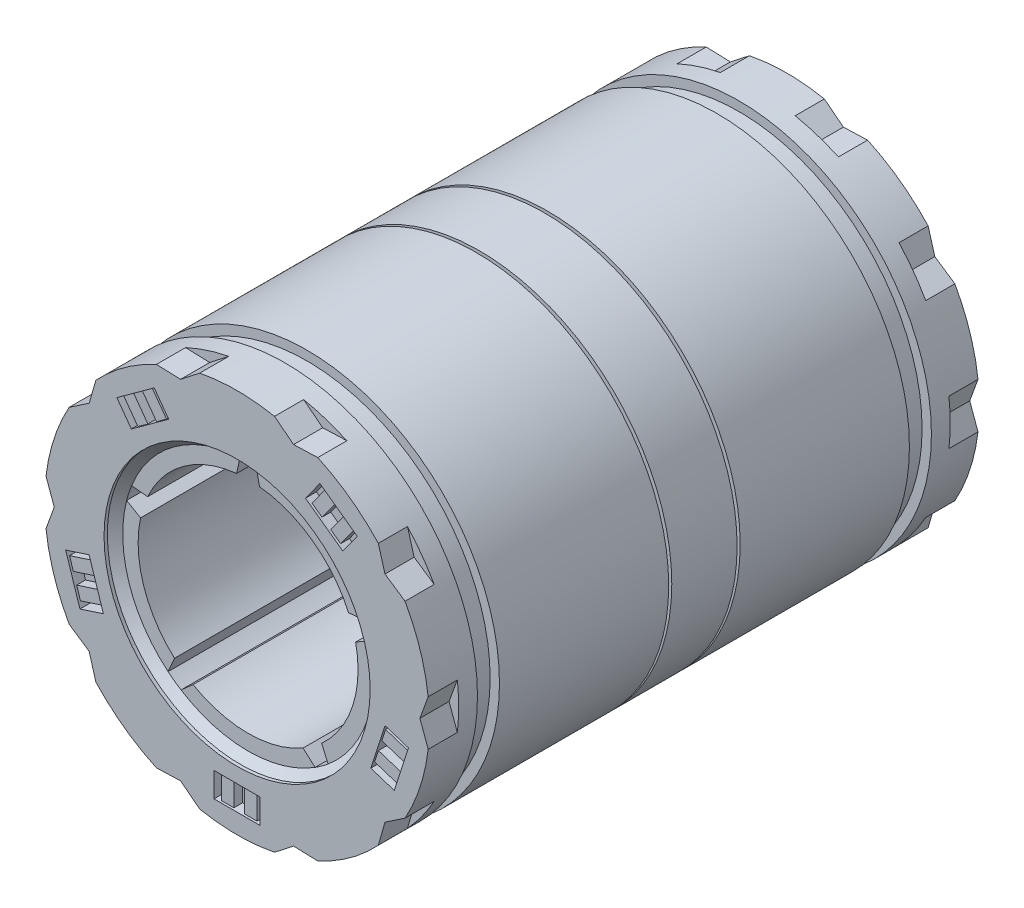
SolidWorks part; units mm, degrees
material "POM Acetal Copolymer"
ref_plane "Front Plane" through (0, 0, 0) normal (0, 0, 1) x (1, 0, 0)
ref_plane "Top Plane" through (0, 0, 0) normal (0, 1, 0) x (1, 0, 0)
ref_plane "Right Plane" through (0, 0, 0) normal (1, 0, 0) x (0, 0, -1)
sketch "Sketch1" plane through (0, 0, 0) normal (0, 0, 1) x (1, 0, 0)
  line L0 (0, 0) -> (-5.5562, -9.6237) construction
  line L2 (5.5562, -9.6237) -> (0, 0) construction
  circle A0 centre (0, 0) radius 11.1125
  circle A1 centre (0, 0) radius 6.35
  point P4 (-3.175, -5.4993)
  point P5 (3.175, -5.4993)
  dimension "OD" = 22.225
  dimension "ID" = 12.7
  dimension "a" = 60
  dimension "Width" = 6.35
sketch "Sketch2" plane through (0, 0, 0) normal (1, 0, 0) x (0, 0, -1)
  line L0 (-15.875, 0) -> (15.875, 0) construction
  line L1 (0, -11.1125) -> (0, 11.1125) construction
  line L3 (-13.1064, 11.1125) -> (-11.8364, 11.1125)
  line L4 (-13.1064, 11.1125) -> (-13.1064, 10.574)
  line L5 (-13.1064, 10.574) -> (-11.8364, 10.574)
  line L6 (-11.8364, 11.1125) -> (-11.8364, 10.574)
  point P3 (-13.1064, 0)
  point P5 (13.1064, 0)
  point P10 (-11.8364, 0)
  dimension "Overall Length" = 31.75
  dimension "Retaining Ring Groove End to End Length" = 26.2128
  dimension "Groove Thickness" = 1.27
  dimension "Groove Depth" = 0.5385
sketch "Sketch3" plane through (0, 0, 0) normal (1, 0, 0) x (0, 0, -1)
  line L0 (-15.875, 6.35) -> (-15.875, 11.1125)
  line L1 (-15.875, 11.1125) -> (-13.1064, 11.1125)
  line L2 (-13.1064, 11.1125) -> (-13.1064, 10.574)
  line L3 (-13.1064, 10.574) -> (-11.8364, 10.574)
  line L4 (-11.8364, 10.574) -> (-11.8364, 11.1125)
  line L5 (-11.8364, 11.1125) -> (-2.0637, 11.1125)
  line L6 (11.8364, 11.1125) -> (11.8364, 10.574)
  line L7 (11.8364, 10.574) -> (13.1064, 10.574)
  line L8 (13.1064, 10.574) -> (13.1064, 11.1125)
  line L9 (13.1064, 11.1125) -> (15.875, 11.1125)
  line L10 (15.875, 11.1125) -> (15.875, 6.35)
  line L11 (15.875, 6.35) -> (-15.875, 6.35)
  line L14 (-2.0637, 11.1125) -> (-2.0637, 10.668)
  line L15 (-2.0637, 10.668) -> (-1.8859, 10.668)
  line L16 (-1.8859, 10.668) -> (-1.8859, 11.1125)
  line L17 (1.886, 11.1125) -> (1.886, 10.668)
  line L18 (1.886, 10.668) -> (2.0638, 10.668)
  line L19 (2.0638, 10.668) -> (2.0638, 11.1125)
  line L20 (-1.8859, 11.1125) -> (1.886, 11.1125)
  line L21 (2.0638, 11.1125) -> (11.8364, 11.1125)
  point P17 (0, 6.35)
  point P30 (0, 11.1125)
  dimension "D1" = 4.1275
  dimension "D2" = 0.4445
  dimension "D3" = 0.1778
revolve "Revolve1" add sketch "Sketch3" angle 360 about L0
sketch "Sketch4" plane through (0, 0, 0) normal (0, 0, 1) x (1, 0, 0)
  line L0 (-3.175, -5.4993) -> (-3.8723, -6.1162)
  line L2 (-6.2112, 1.3202) -> (-7.0135, 1.7928)
  line L3 (3.175, -5.4993) -> (3.8723, -6.1162)
  line L5 (-4.249, -4.719) -> (-4.6202, -5.5728)
  line L6 (-0.6638, 6.3152) -> (-0.4622, 7.2242)
  line L7 (-5.801, 2.5828) -> (-6.7278, 2.672)
  line L8 (5.801, 2.5828) -> (6.7278, 2.672)
  line L9 (0.6638, 6.3152) -> (0.4622, 7.2242)
  line L10 (4.249, -4.719) -> (4.6202, -5.5728)
  line L11 (6.2112, 1.3202) -> (7.0135, 1.7928)
  arc A0 (0.4622, 7.2242) -> (-0.4622, 7.2242) centre (0, 0) ccw
  circle A1 centre (0, 0) radius 6.35 construction
  arc A2 (-5.801, 2.5828) -> (-6.2112, 1.3202) centre (0, 0) ccw
  arc A11 (-6.7278, 2.672) -> (-7.0135, 1.7928) centre (0, 0) ccw
  arc A12 (-7.0204, 1.7657) -> (-4.6418, -5.5549) centre (0, 0) ccw construction
  arc A13 (4.6418, -5.5549) -> (7.0204, 1.7657) centre (0, 0) ccw construction
  arc A14 (6.7174, 2.698) -> (0.4902, 7.2224) centre (0, 0) ccw construction
  arc A15 (4.249, -4.719) -> (6.2112, 1.3202) centre (0, 0) ccw construction
  arc A16 (5.801, 2.5828) -> (0.6638, 6.3152) centre (0, 0) ccw construction
  arc A17 (-0.6638, 6.3152) -> (-5.801, 2.5828) centre (0, 0) ccw construction
  arc A18 (-6.2112, 1.3202) -> (-4.249, -4.719) centre (0, 0) ccw construction
  arc A19 (-0.4902, 7.2224) -> (-6.7174, 2.698) centre (0, 0) ccw construction
  arc A20 (7.0135, 1.7928) -> (6.7278, 2.672) centre (0, 0) ccw
  arc A21 (3.8723, -6.1162) -> (4.6202, -5.5728) centre (0, 0) ccw
  arc A22 (-4.6202, -5.5728) -> (-3.8723, -6.1162) centre (0, 0) ccw
  arc A23 (0.6638, 6.3152) -> (-0.6638, 6.3152) centre (0, 0) ccw
  arc A24 (6.2112, 1.3202) -> (5.801, 2.5828) centre (0, 0) ccw
  arc A25 (3.175, -5.4993) -> (4.249, -4.719) centre (0, 0) ccw
  arc A26 (-4.249, -4.719) -> (-3.175, -5.4993) centre (0, 0) ccw
  point P31 (0, 0)
  dimension "D1" = 0.889
  dimension "D3" = 25
  dimension "D2" = 5
extrude "Cut-Extrude1" cut sketch "Sketch4" against normal through all both and the other way through all
sketch "Sketch5" plane through (0, 0, 0) normal (0, 0, 1) x (1, 0, 0)
  circle A0 centre (0, 0) radius 7.6835
  circle A1 centre (0, 0) radius 6.35 construction
  dimension "D1" = 1.3335
extrude "Cut-Extrude2" cut sketch "Sketch5" against normal blind 0.635 from surface starting at face at (0, 0, 15.875)
extrude "Cut-Extrude3" cut sketch "Sketch5<2>" along normal blind 0.635 from surface starting at face at (11.1125, 0, -15.875)
sketch "Sketch5<2>" plane through (0, 0, 0) normal (0, 0, 1) x (1, 0, 0) same geometry as "Sketch5"
chamfer "Chamfer1" distance 0.4445 angle 45 2 edges at (-7.6835, 0, 15.24) (7.6835, 0, -15.24)
sketch "Sketch8" plane through (0, 0, 0) normal (0, 0, 1) x (1, 0, 0)
  line L0 (-4.6584, 10.0889) -> (-3.2623, 10.0402)
  line L1 (-3.2623, 10.0402) -> (-2.1614, 10.9003)
  line L2 (0, 0) -> (0, 10.5569) construction
  line L3 (0, 0) -> (-3.2623, 10.0402) construction
  line L4 (2.1614, 10.9003) -> (3.2623, 10.0402)
  line L5 (3.2623, 10.0402) -> (4.6584, 10.0889)
  line L6 (8.1556, 7.5481) -> (8.5407, 6.2052)
  line L7 (8.5407, 6.2052) -> (9.6989, 5.424)
  line L8 (11.0347, 1.3128) -> (10.5569, 0)
  line L9 (10.5569, 0) -> (11.0347, -1.3128)
  line L10 (9.6989, -5.424) -> (8.5407, -6.2052)
  line L11 (8.5407, -6.2052) -> (8.1556, -7.5481)
  line L12 (4.6584, -10.0889) -> (3.2623, -10.0402)
  line L13 (3.2623, -10.0402) -> (2.1614, -10.9003)
  line L14 (-2.1614, -10.9003) -> (-3.2623, -10.0402)
  line L15 (-3.2623, -10.0402) -> (-4.6584, -10.0889)
  line L16 (-8.1556, -7.5481) -> (-8.5407, -6.2052)
  line L17 (-8.5407, -6.2052) -> (-9.6989, -5.424)
  line L18 (-11.0347, -1.3128) -> (-10.5569, 0)
  line L19 (-10.5569, 0) -> (-11.0347, 1.3128)
  line L20 (-9.6989, 5.424) -> (-8.5407, 6.2052)
  line L21 (-8.5407, 6.2052) -> (-8.1556, 7.5481)
  circle A0 centre (0, 0) radius 11.1125 construction
  circle A1 centre (0, 0) radius 10.5569 construction
  arc A2 (-2.1614, 10.9003) -> (-4.6584, 10.0889) centre (0, 0) ccw
  arc A3 (4.6584, 10.0889) -> (2.1614, 10.9003) centre (0, 0) ccw
  arc A4 (9.6989, 5.424) -> (8.1556, 7.5481) centre (0, 0) ccw
  arc A5 (11.0347, -1.3128) -> (11.0347, 1.3128) centre (0, 0) ccw
  arc A6 (8.1556, -7.5481) -> (9.6989, -5.424) centre (0, 0) ccw
  arc A7 (2.1614, -10.9003) -> (4.6584, -10.0889) centre (0, 0) ccw
  arc A8 (-4.6584, -10.0889) -> (-2.1614, -10.9003) centre (0, 0) ccw
  arc A9 (-9.6989, -5.424) -> (-8.1556, -7.5481) centre (0, 0) ccw
  arc A10 (-11.0347, 1.3128) -> (-11.0347, -1.3128) centre (0, 0) ccw
  arc A11 (-8.1556, 7.5481) -> (-9.6989, 5.424) centre (0, 0) ccw
  point P38 (0, 0)
  dimension "D1" = 140
  dimension "D2" = 0.5556
  dimension "D3" = 10
extrude "Cut-Extrude5" cut sketch "Sketch8" against normal blind 1.6827 from surface starting at face at (-7.6835, 0, 15.875)
extrude "Cut-Extrude6" cut sketch "Sketch8<2>" along normal blind 1.6827 from surface starting at face at (7.6835, 0, -15.875)
sketch "Sketch8<2>" plane through (0, 0, 0) normal (0, 0, 1) x (1, 0, 0) same geometry as "Sketch8"
sketch "Sketch9" plane through (0, 0, 0) normal (0, 0, 1) x (1, 0, 0)
  line L0 (0, -11.1125) -> (0, -9.9746) construction
  line L1 (-1.3335, -8.5522) -> (-1.0223, -8.5522)
  line L2 (-1.3335, -8.5522) -> (-1.3335, -9.9746)
  line L3 (-1.3335, -9.9746) -> (-1.0223, -9.9746)
  line L4 (1.3335, -8.5522) -> (1.3335, -9.9746)
  line L5 (-1.0223, -8.5522) -> (-1.0223, -9.9746)
  line L6 (-1.3335, -9.2634) -> (-1.0224, -9.2634) construction
  line L7 (-0.3111, -8.5522) -> (-0.3111, -9.9746)
  line L8 (-1.0224, -9.2634) -> (-0.3111, -9.2634) construction
  line L9 (0.3111, -8.5522) -> (0.3111, -9.9746)
  line L10 (-0.3111, -9.2634) -> (0, -9.2634) construction
  line L11 (1.0224, -8.5522) -> (1.0224, -9.9746)
  line L12 (0.3111, -9.2634) -> (1.0224, -9.2634) construction
  line L13 (1.0224, -9.2634) -> (1.3335, -9.2634) construction
  line L14 (0, -9.2634) -> (0.3111, -9.2634) construction
  line L15 (-0.3111, -8.5522) -> (0.3111, -8.5522)
  line L16 (1.0224, -8.5522) -> (1.3335, -8.5522)
  line L17 (1.0224, -9.9746) -> (1.3335, -9.9746)
  line L18 (-0.3111, -9.9746) -> (0.3111, -9.9746)
  circle A1 centre (0, 0) radius 11.1125 construction
  dimension "D1" = 2.667
  dimension "D2" = 1.4224
  dimension "D3" = 1.1379
  dimension "D4" = 0.7112
extrude "Cut-Extrude7" cut sketch "Sketch9" against normal blind 0.635 from surface starting at face at (-7.6835, 0, 15.875)
sketch "Sketch10" plane through (0, 0, 0) normal (0, 0, 1) x (1, 0, 0)
  line L1 (-1.3335, -8.5522) -> (1.3335, -8.5522)
  line L2 (-1.3335, -8.5522) -> (-1.3335, -9.9746)
  line L3 (-1.3335, -9.9746) -> (1.3335, -9.9746)
  line L4 (1.3335, -8.5522) -> (1.3335, -9.9746)
extrude "Cut-Extrude8" cut sketch "Sketch10" against normal blind 0.127 from surface starting at face at (-1.1779, -9.2634, 15.875)
extrude "Cut-Extrude9" cut sketch "Sketch9<2>" along normal blind 0.635 from surface starting at face at (7.6835, 0, -15.875)
sketch "Sketch9<2>" plane through (0, 0, 0) normal (0, 0, 1) x (1, 0, 0) same geometry as "Sketch9"
extrude "Cut-Extrude11" cut sketch "Sketch10<2>" along normal blind 0.127 from surface starting at face at (1.1779, -9.2634, -15.875)
sketch "Sketch10<2>" plane through (0, 0, 0) normal (0, 0, 1) x (1, 0, 0) same geometry as "Sketch10"
pattern_circular "CirPattern2" count 5 over 360 about axis through (0, 0, 15.875) along (0, 0, 1) of "Cut-Extrude7", "Cut-Extrude8", "Cut-Extrude9", "Cut-Extrude11"
sketch "Sketch6" [suppressed] plane through (0, 0, 0) normal (0, 1, 0) x (1, 0, 0)
  line L0 (-1.2319, 12.0269) -> (-1.2319, -12.0269)
  line L1 (-1.9431, 12.0269) -> (-1.9431, -12.0269)
  line L2 (-1.9431, -12.7381) -> (-1.9431, -12.0269) construction
  line L3 (-1.2319, 0) -> (-1.9431, 0) construction
  line L4 (-3.175, 0) -> (-1.5875, 0) construction
  line L5 (-3.175, 15.24) -> (-3.175, -15.24) construction
  line L6 (-1.5875, 0) -> (0, 0) construction
  line L7 (0, 0) -> (1.5875, 0) construction
  line L8 (1.5875, 0) -> (3.175, 0) construction
  line L9 (3.175, 15.24) -> (3.175, -15.24) construction
  line L10 (0, -15.875) -> (0, 15.875) construction
  line L11 (0, -15.875) -> (0, 15.875) construction
  line L12 (1.2319, 0) -> (1.9431, 0) construction
  line L13 (1.9431, -12.7381) -> (1.9431, -12.0269) construction
  line L14 (1.9431, 12.0269) -> (1.9431, -12.0269)
  line L15 (1.2319, 12.0269) -> (1.2319, -12.0269)
  arc A0 (-1.9431, -12.0269) -> (-1.9431, -12.7381) centre (-1.9431, -12.3825) ccw
  arc A1 (-1.2319, -12.0269) -> (-1.9431, -12.7381) centre (-1.9431, -12.0269) cw
  arc A2 (-1.9431, 12.0269) -> (-1.9431, 12.7381) centre (-1.9431, 12.3825) cw
  arc A3 (-1.2319, 12.0269) -> (-1.9431, 12.7381) centre (-1.9431, 12.0269) ccw
  arc A4 (1.2319, 12.0269) -> (1.9431, 12.7381) centre (1.9431, 12.0269) cw
  arc A5 (1.9431, 12.0269) -> (1.9431, 12.7381) centre (1.9431, 12.3825) ccw
  arc A6 (1.2319, -12.0269) -> (1.9431, -12.7381) centre (1.9431, -12.0269) ccw
  arc A7 (1.9431, -12.0269) -> (1.9431, -12.7381) centre (1.9431, -12.3825) cw
  point P7 (-1.2319, 0)
  point P8 (-1.9431, 0)
  point P11 (-1.5875, 0)
  dimension "D1" = 0.7112
  dimension "D2" = 12.3825
extrude "Cut-Extrude4" [suppressed] cut sketch "Sketch6" against normal up to surface (7.1334 mm away)
sketch "Sketch7" [suppressed] plane through (0, 0, 0) normal (0, 0, 1) x (1, 0, 0)
  line L0 (0, -6.35) -> (0, -7.239) construction
  line L1 (-1.2319, 0) -> (-1.2319, -6.6819) construction
  line L2 (-1.9431, 0) -> (-1.9431, -6.5107) construction
  line L3 (-1.9431, -6.5107) -> (-1.5898, -6.6059) construction
  line L4 (-1.5898, -6.6059) -> (-1.2319, -6.6819) construction
  line L6 (-2.0135, -6.4714) -> (-1.1559, -6.7024)
  line L8 (-1.5898, -6.6059) -> (-1.5847, -6.5869) construction
  circle A0 centre (0, 0) radius 6.7945 construction
  arc A1 (-3.175, -5.4993) -> (3.175, -5.4993) centre (0, 0) ccw construction
  arc A2 (-3.8723, -6.1162) -> (3.8723, -6.1162) centre (0, 0) ccw construction
  circle A3 centre (-1.5898, -6.6059) radius 0.4445 construction
  arc A5 (-1.1559, -6.7024) -> (-2.0135, -6.4714) centre (-1.5898, -6.6059) ccw
  point P11 (0, -6.7945)
revolve "Revolve3" [suppressed] add sketch "Sketch7" angle 360 about L6
pattern_linear "LPattern1" [suppressed] count 15 spacing 0.8819 along (0, 0, 1) count 15 spacing 0.8819 along (0, 0, -1) of bodies 110
mirror "Mirror1" [suppressed] about plane through (0, 0, 0) normal (1, 0, 0)
pattern_circular "CirPattern1" [suppressed] count 5 over 360 about axis through (0, 0, 15.875) along (0, 0, -1) of bodies 112
equation "\"D1@Sketch3\"=\"Overall Length@Sketch2\"*.13"
equation "\"D2@Sketch3\"=\"OD@Sketch1\"*.02"
equation "\"D3@Sketch3\"=\"Overall Length@Sketch2\"*.0056"
equation "\"D1@Sketch4\"=\"OD@Sketch1\"*.04"
equation "\"D1@Sketch5\"=\"OD@Sketch1\"*.06"
equation "\"D1@Cut-Extrude2\"=.02*\"Overall Length@Sketch2\""
equation "\"D1@Cut-Extrude3\"=.02*\"Overall Length@Sketch2\""
equation "\"D1@Sketch6\"= .08*.4*\"OD@Sketch1\""
equation "\"D2@Sketch6\"=.39*\"Overall Length@Sketch2\""
equation "\"D1@Chamfer1\"=\"OD@Sketch1\"*.02"
equation "\"D4@LPattern1\"=\"Overall Length@Sketch2\"* .0277777778"
equation "\"D3@LPattern1\"=\"Overall Length@Sketch2\"* .0277777778"
equation "\"D2@Sketch8\"=\"OD@Sketch1\"*.025"
equation "\"D1@Cut-Extrude5\"=.053*\"Overall Length@Sketch2\""
equation "\"D1@Cut-Extrude6\"=.053*\"Overall Length@Sketch2\""
equation "\"D1@Sketch9\"=\"OD@Sketch1\"*.12"
equation "\"D2@Sketch9\"=\"OD@Sketch1\"*.064"
equation "\"D3@Sketch9\"=\"OD@Sketch1\"*.0512"
equation "\"D4@Sketch9\"=\"OD@Sketch1\"* .032"
equation "\"D1@Cut-Extrude7\"=.02*\"Overall Length@Sketch2\""
equation "\"D1@Cut-Extrude9\"=.02*\"Overall Length@Sketch2\""
